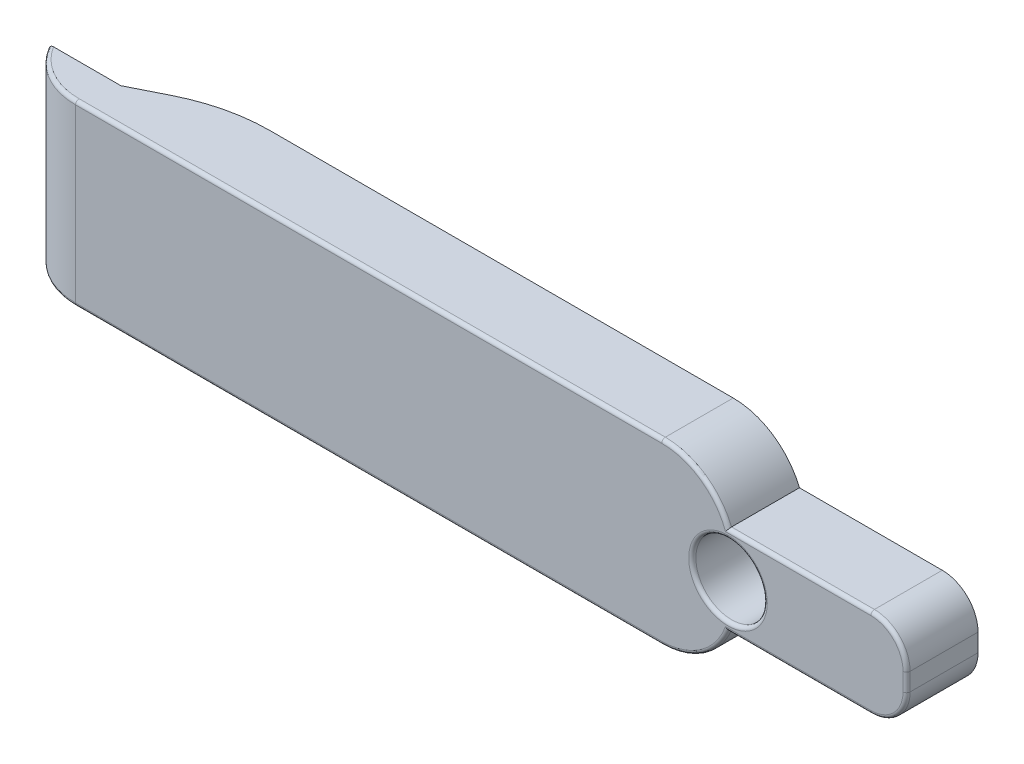
SolidWorks part; units mm, degrees
ref_plane "Front Plane" through (0, 0, 0) normal (0, 0, 1) x (1, 0, 0)
ref_plane "Top Plane" through (0, 0, 0) normal (0, 1, 0) x (1, 0, 0)
ref_plane "Right Plane" through (0, 0, 0) normal (1, 0, 0) x (0, 0, -1)
sketch "Sketch1" plane through (0, 0, 0) normal (0, 0, 1) x (1, 0, 0)
  line L1 (-125, 12.5) -> (125, 12.5)
  line L2 (-125, 12.5) -> (-125, -12.5)
  line L3 (-125, -12.5) -> (125, -12.5)
  line L4 (125, 12.5) -> (125, -12.5)
  line L5 (-125, 12.5) -> (125, -12.5) construction
  line L6 (-125, -12.5) -> (125, 12.5) construction
  point P0 (0, 0)
  dimension "D1" = 250
  dimension "D2" = 25
extrude "Boss-Extrude3" add sketch "Sketch1" along normal blind 20
sketch "Sketch4" plane through (0, 0, 20) normal (0, 0, 1) x (1, 0, 0)
  line L0 (-125, 0) -> (75, 0) construction
  line L1 (-125, 12.5) -> (-125, -12.5) construction
  circle A0 centre (75, 0) radius 10
  dimension "D2" = 20
  dimension "D1" = 200
extrude "Cut-Extrude3" cut sketch "Sketch4" against normal blind 20
sketch "Sketch6" plane through (0, 12.5, 0) normal (0, 1, 0) x (1, 0, 0)
  line L0 (125, -20) -> (-125, -20) construction
  line L1 (-125, 0) -> (75, 0)
  line L2 (-125, 0) -> (-125, -20)
  line L3 (-125, -20) -> (75, -20)
  line L4 (75, 0) -> (75, -20)
  dimension "D1" = 200
extrude "Boss-Extrude4" add sketch "Sketch6" along normal blind 12.5
sketch "Sketch7" plane through (0, -12.5, 0) normal (0, -1, 0) x (1, 0, 0)
  line L0 (-125, 0) -> (125, 0) construction
  line L1 (-125, 20) -> (75, 20)
  line L2 (-125, 20) -> (-125, 0)
  line L3 (-125, 0) -> (75, 0)
  line L4 (75, 20) -> (75, 0)
  dimension "D1" = 200
extrude "Boss-Extrude5" add sketch "Sketch7" along normal blind 12.5
sketch "Sketch8" plane through (0, 25, 0) normal (0, 1, 0) x (1, 0, 0)
  line L0 (-125, -20) -> (75, -20) construction
  line L1 (-125, 0) -> (-85, 0)
  line L2 (-125, 0) -> (-125, -20)
  line L3 (-125, -20) -> (-85, -20)
  line L4 (-85, 0) -> (-85, -20)
  line L6 (-125, -10) -> (-85, -10)
  line L7 (-105, -10) -> (-85, 0)
  line M5 (-125, 0) -> (-125, -20)
  line M8 (75, 0) -> (-125, 0)
  dimension "D1" = 40
extrude "Cut-Extrude8" cut sketch "Sketch8" against normal through all contours L6 L7 M8 M5 region at (-109.4444, 25, 4.4444)
fillet "Fillet10" radius 20 1 edges at (-125, 0, 20)
fillet "Fillet11" radius 20 2 edges at (75, -25, 10) (75, 25, 10)
fillet "Fillet12" radius 10 2 edges at (125, 12.5, 10) (125, -12.5, 10)
fillet "Fillet13" radius 50 1 edges at (-85, 0, 0)
fillet "Fillet15" radius 1 12 edges at (-117.6795, -25, 17.3205) (-117.6795, 25, 17.3205) (122.0711, -9.5711, 20) (95, -12.5, 20) (67.6398, -21.5831, 20) (-25.61, -25, 20) (-25.61, 25, 20) (67.6398, 21.5831, 20) (95, 12.5, 20) (122.0711, 9.5711, 20) (125, 0, 20) (85, 0, 20)
